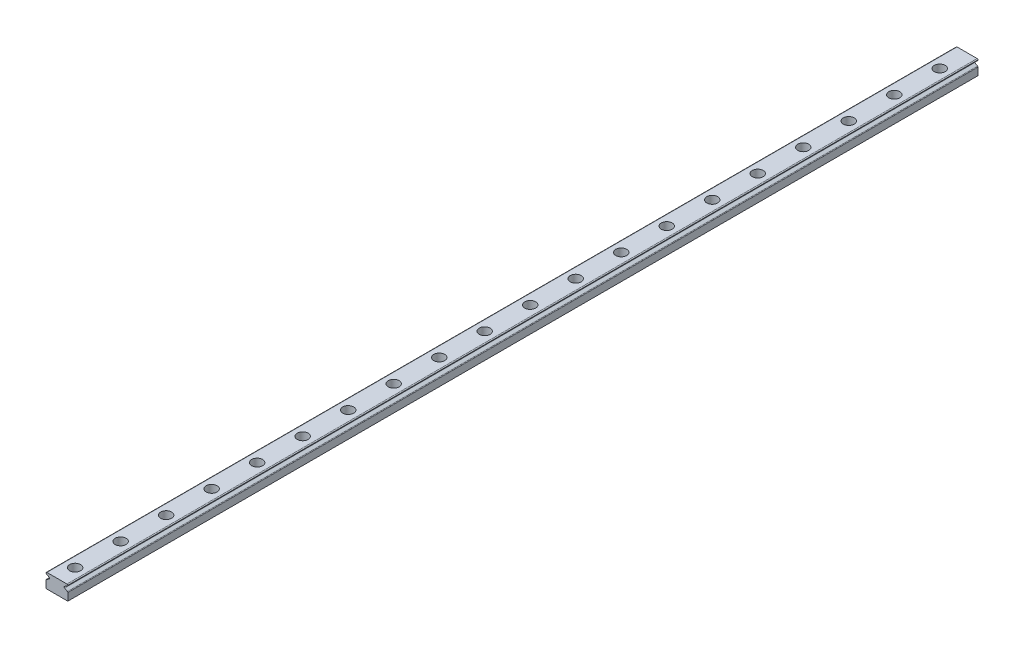
SolidWorks part; units mm, degrees
material "Plain Carbon Steel"
ref_plane "Front Plane" through (0, 0, 0) normal (0, 0, 1) x (1, 0, 0)
ref_plane "Top Plane" through (0, 0, 0) normal (0, 1, 0) x (1, 0, 0)
ref_plane "Right Plane" through (0, 0, 0) normal (1, 0, 0) x (0, 0, -1)
sketch "Sketch1" plane through (0, 0, 0) normal (0, 0, 1) x (1, 0, 0)
  line L4 (0, 0) -> (12, 0)
  line L5 (12, 0) -> (12, 8.4034)
  line L6 (12, 12) -> (0, 12)
  line L7 (0, 12) -> (0, 11.2902)
  line L8 (6, 12) -> (6, 7.6937) construction
  line L9 (6, 7.6937) -> (0, 7.6937) construction
  line L10 (0, 7.6937) -> (12, 7.6937) construction
  line L11 (6, 9.8468) -> (2.5, 9.8468) construction
  line L12 (6, 9.8468) -> (9.5, 9.8468) construction
  line L13 (9.5, 9.8468) -> (12, 11.2902)
  line L22 (9.5, 9.8468) -> (12, 8.4034)
  line L23 (2.5, 9.8468) -> (0, 11.2902)
  line L24 (2.5, 9.8468) -> (0, 8.4034)
  line L27 (12, 11.2902) -> (12, 12)
  line L28 (0, 8.4034) -> (0, 0)
  line L29 (7, 12) -> (7, 0) construction
  dimension "D3" = 3.5
  dimension "D1" = 6
  dimension "D2" = 7.6937
  dimension "D4" = 30
  dimension "D5" = 30
  dimension "D6" = 30
  dimension "D7" = 30
  dimension "D9" = 12
  dimension "D10" = 5
  dimension "D11" = 3.5
extrude "Boss-Extrude2" add sketch "Sketch1" along normal blind 500
fillet "Fillet5" radius 0.5 8 edges at (9.5, 9.8468, 250) (0, 12, 250) (12, 12, 250) (2.5, 9.8468, 250) (12, 8.4034, 250) (0, 8.4034, 250) (12, 11.2902, 250) (0, 11.2902, 250)
sketch "Sketch3" plane through (0, 12, 0) normal (0, 1, 0) x (1, 0, 0)
  line L0 (6, -500) -> (6, -490) construction
  line L1 (11.5, -500) -> (0.5, -500) construction
  line L2 (6, -490) -> (6, -440) construction
  line L3 (6, -440) -> (6, -465) construction
  circle A0 centre (6, -490) radius 3
  circle A1 centre (6, -440) radius 3
  circle A2 centre (6, -415) radius 3
  circle A3 centre (6, -390) radius 3
  circle A4 centre (6, -365) radius 3
  circle A5 centre (6, -340) radius 3
  circle A6 centre (6, -315) radius 3
  circle A7 centre (6, -290) radius 3
  circle A8 centre (6, -265) radius 3
  circle A9 centre (6, -240) radius 3
  circle A10 centre (6, -215) radius 3
  circle A11 centre (6, -190) radius 3
  circle A12 centre (6, -165) radius 3
  circle A13 centre (6, -140) radius 3
  circle A14 centre (6, -115) radius 3
  circle A15 centre (6, -90) radius 3
  circle A16 centre (6, -65) radius 3
  circle A17 centre (6, -40) radius 3
  circle A18 centre (6, -15) radius 3
  circle A19 centre (6, -465) radius 3
  dimension "D1" = 18
extrude "Cut-Extrude2" cut sketch "Sketch3" against normal blind 4.5
sketch "Sketch4" plane through (0, 12, 0) normal (0, 1, 0) x (1, 0, 0)
  line L0 (6, 0) -> (6, -15) construction
  line L1 (11.5, 0) -> (0.5, 0) construction
  circle A0 centre (6, -15) radius 1.75
  circle A1 centre (6, -40) radius 1.75
  circle A2 centre (6, -65) radius 1.75
  circle A3 centre (6, -90) radius 1.75
  circle A4 centre (6, -115) radius 1.75
  circle A5 centre (6, -140) radius 1.75
  circle A6 centre (6, -165) radius 1.75
  circle A7 centre (6, -190) radius 1.75
  circle A8 centre (6, -215) radius 1.75
  circle A9 centre (6, -240) radius 1.75
  circle A10 centre (6, -265) radius 1.75
  circle A11 centre (6, -290) radius 1.75
  circle A12 centre (6, -315) radius 1.75
  circle A13 centre (6, -340) radius 1.75
  circle A14 centre (6, -365) radius 1.75
  circle A15 centre (6, -390) radius 1.75
  circle A16 centre (6, -415) radius 1.75
  circle A17 centre (6, -440) radius 1.75
  circle A18 centre (6, -465) radius 1.75
  circle A19 centre (6, -490) radius 1.75
  dimension "D1" = 20
extrude "Cut-Extrude3" cut sketch "Sketch4" against normal blind 14.5
sketch "Sketch5" plane through (0, 0, 0) normal (0, 0, -1) x (-1, 0, 0)
  line L0 (-12, 0) -> (-12, 4.0574)
  line L2 (-12, 0) -> (-12, 8.1148) construction
  line L3 (-12, 4.0574) -> (0, 4.0574)
  line L4 (0, 8.1148) -> (0, 0) construction
  line L5 (0, 4.0574) -> (0, 0)
  line L6 (0, 0) -> (-12, 0)
extrude "Cut-Extrude4" cut sketch "Sketch5" against normal blind 682.5
